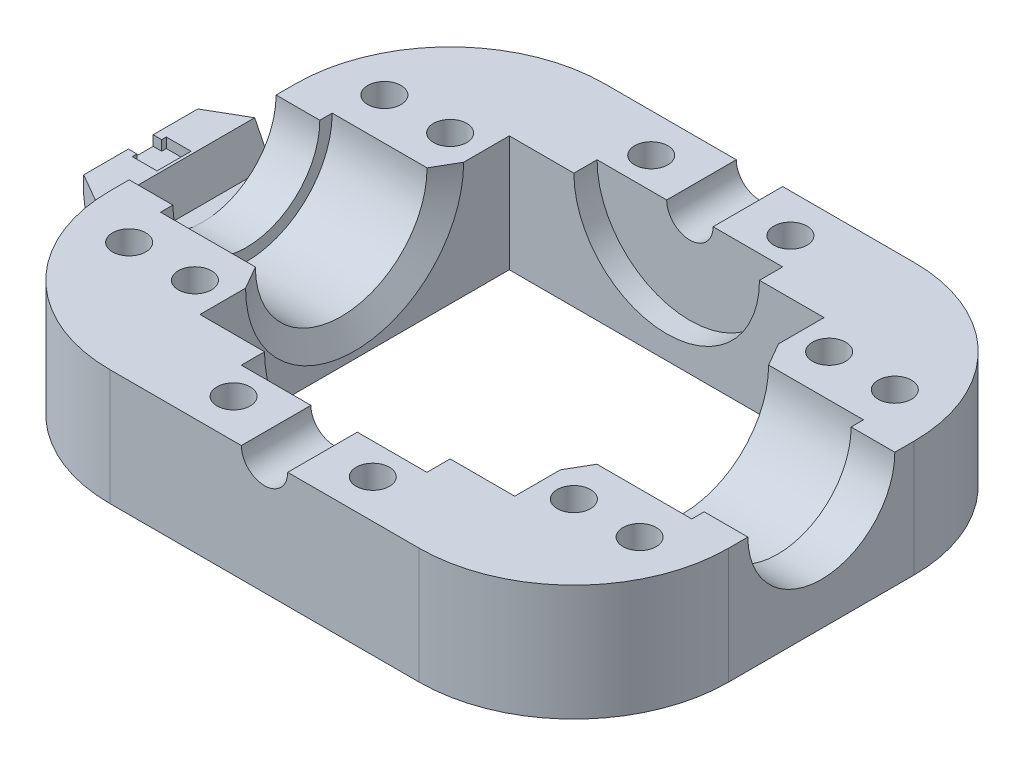
SolidWorks part; units mm, degrees
ref_plane "Спереди" through (0, 0, 0) normal (0, 0, 1) x (1, 0, 0)
ref_plane "Сверху" through (0, 0, 0) normal (0, 1, 0) x (1, 0, 0)
ref_plane "Справа" through (0, 0, 0) normal (1, 0, 0) x (0, 0, -1)
sketch "Sketch1" plane through (0, 0, 0) normal (0, 1, 0) x (1, 0, 0)
  line L1 (40, -32) -> (-40, -32)
  line L2 (40, -32) -> (40, 32)
  line L3 (40, 32) -> (-40, 32)
  line L4 (-40, -32) -> (-40, 32)
  line L5 (40, -32) -> (-40, 32) construction
  line L6 (40, 32) -> (-40, -32) construction
  line L7 (20.35, -20) -> (-20.35, -20)
  line L8 (20.35, -20) -> (20.35, 20)
  line L9 (20.35, 20) -> (-20.35, 20)
  line L10 (-20.35, -20) -> (-20.35, 20)
  line L11 (20.35, -20) -> (-20.35, 20) construction
  line L12 (20.35, 20) -> (-20.35, -20) construction
  point P0 (0, 0)
  point P6 (0, 0)
  dimension "D1" = 80
  dimension "D2" = 64
  dimension "D3" = 40
  dimension "D4" = 40.7
extrude "Boss-Extrude1" add sketch "Sketch1" along normal blind 15
sketch "Sketch3" plane through (0, 15, 0) normal (0, 1, 0) x (1, 0, 0)
  line L0 (-20.35, 0) -> (-40, 0) construction
  line L1 (-20.35, 20) -> (-20.35, -20) construction
  line L2 (-40, 32) -> (-40, -32) construction
  line L3 (20.35, 0) -> (40, 0) construction
  line L4 (20.35, -20) -> (20.35, 20) construction
  line L5 (40, -32) -> (40, 32) construction
  line L10 (20.35, -11.1) -> (34.35, -11.1)
  line L11 (20.35, -11.1) -> (20.35, 0)
  line L12 (20.35, 0) -> (34.35, 0)
  line L13 (34.35, -11.1) -> (34.35, 0)
  line L14 (20.35, -11.1) -> (34.35, 0) construction
  line L15 (20.35, 0) -> (34.35, -11.1) construction
  line L16 (-34.35, -11.1) -> (-20.35, -11.1)
  line L17 (-34.35, -11.1) -> (-34.35, 0)
  line L18 (-34.35, 0) -> (-20.35, 0)
  line L19 (-20.35, -11.1) -> (-20.35, 0)
  line L20 (-34.35, -11.1) -> (-20.35, 0) construction
  line L21 (-34.35, 0) -> (-20.35, -11.1) construction
  point P18 (27.35, -5.55)
  point P23 (-27.35, -5.55)
  dimension "D1" = 14
  dimension "D2" = 11.1
revolve "Cut-Revolve1" cut sketch "Sketch3" angle 360 about L12
sketch "Sketch4" plane through (40, 0, 0) normal (1, 0, 0) x (0, 0, -1)
  line L0 (-32, 15) -> (32, 15) construction
  circle A0 centre (0, 15) radius 9.5
  dimension "D1" = 19
extrude "Cut-Extrude2" cut sketch "Sketch4" against normal through all
sketch "Sketch5" plane through (0, 0, 32) normal (0, 0, 1) x (1, 0, 0)
  line L0 (-40, 15) -> (40, 15) construction
  circle A0 centre (0, 15) radius 3
  dimension "D1" = 6
extrude "Cut-Extrude3" cut sketch "Sketch5" against normal through all
sketch "Sketch8" plane through (0, 15, 0) normal (0, 1, 0) x (1, 0, 0)
  line L1 (-24.5, -16.5) -> (24.5, -16.5) construction
  line L2 (-24.5, -16.5) -> (-24.5, 16.5) construction
  line L3 (-24.5, 16.5) -> (24.5, 16.5) construction
  line L4 (24.5, -16.5) -> (24.5, 16.5) construction
  line L5 (-24.5, -16.5) -> (24.5, 16.5) construction
  line L6 (-24.5, 16.5) -> (24.5, -16.5) construction
  line L7 (-9, 27) -> (9, 27) construction
  line L8 (-9, 27) -> (-9, -27) construction
  line L9 (-9, -27) -> (9, -27) construction
  line L10 (9, 27) -> (9, -27) construction
  line L11 (-9, 27) -> (9, -27) construction
  line L12 (-9, -27) -> (9, 27) construction
  line L13 (33, -16.5) -> (-33, -16.5) construction
  line L14 (33, -16.5) -> (33, 16.5) construction
  line L15 (33, 16.5) -> (-33, 16.5) construction
  line L16 (-33, -16.5) -> (-33, 16.5) construction
  line L17 (33, -16.5) -> (-33, 16.5) construction
  line L18 (33, 16.5) -> (-33, -16.5) construction
  circle A0 centre (24.5, 16.5) radius 2.15
  circle A1 centre (24.5, -16.5) radius 2.15
  circle A2 centre (-24.5, -16.5) radius 2.15
  circle A3 centre (-24.5, 16.5) radius 2.15
  circle A4 centre (9, -27) radius 2.15
  circle A5 centre (-9, -27) radius 2.15
  circle A6 centre (-9, 27) radius 2.15
  circle A7 centre (9, 27) radius 2.15
  circle A8 centre (-33, 16.5) radius 2.15
  circle A9 centre (-33, -16.5) radius 2.15
  circle A10 centre (33, -16.5) radius 2.15
  circle A11 centre (33, 16.5) radius 2.15
  point P0 (0, 0)
  point P10 (0, 0)
  point P16 (0, 0)
  dimension "D3" = 4.3
  dimension "D1" = 33
  dimension "D2" = 49
  dimension "D4" = 18
  dimension "D5" = 54
  dimension "D6" = 66
extrude "Cut-Extrude6" cut sketch "Sketch8" against normal through all
fillet "Fillet1" radius 20 4 edges at (-40, 7.5, 32) (-40, 7.5, -32) (40, 7.5, -32) (40, 7.5, 32)
chamfer "Chamfer1" distance 3 angle 30 2 edges at (-20.35, 3.9, 0) (20.35, 3.9, 0) first distance on face at (-20.35, 8.15, 0) first distance on face at (20.35, 8.15, 0)
sketch "Sketch9" plane through (0, 15, 0) normal (0, 1, 0) x (1, 0, 0)
  line L0 (0, 29.8714) -> (0, -31.0419) construction
  line L1 (-3, 20) -> (-20.35, 20) construction
  line L2 (-12, -23) -> (0, -23)
  line L3 (-12, -23) -> (-12, -20)
  line L4 (-12, -20) -> (0, -20)
  line L5 (0, -23) -> (0, -20)
  line L6 (-12, -23) -> (0, -20) construction
  line L7 (-12, -20) -> (0, -23) construction
  line L8 (-12, 20) -> (0, 20)
  line L9 (-12, 20) -> (-12, 23)
  line L10 (-12, 23) -> (0, 23)
  line L11 (0, 20) -> (0, 23)
  line L12 (-12, 20) -> (0, 23) construction
  line L13 (-12, 23) -> (0, 20) construction
  line L14 (-20.35, -20) -> (-3, -20) construction
  point P3 (-6, -21.5)
  point P8 (-6, 21.5)
  dimension "D1" = 3
  dimension "D2" = 12
revolve "Cut-Revolve2" cut sketch "Sketch9" angle 360 about L0 other way angle 360
sketch "Sketch10" plane through (-40, 0, 0) normal (-1, 0, 0) x (0, 0, 1)
  line L0 (-9.5, 15) -> (9.5, 15) construction
  line L1 (0, 15) -> (0, 0) construction
  line L2 (-12, 0) -> (12, 0) construction
  line L4 (12, 5.5) -> (-12, 5.5)
  line L5 (12, 5.5) -> (12, 0)
  line L6 (12, 0) -> (-12, 0)
  line L7 (-12, 5.5) -> (-12, 0)
  line L8 (12, 5.5) -> (-12, 0) construction
  line L9 (12, 0) -> (-12, 5.5) construction
  arc A0 (-9.5, 15) -> (9.5, 15) centre (0, 15) ccw construction
  point P8 (0, 2.75)
extrude "Boss-Extrude2" add sketch "Sketch10" along normal blind 8
sketch "Sketch12" plane through (-40, 0, 0) normal (-1, 0, 0) x (0, 0, 1)
  line L0 (-9.5, 15) -> (9.5, 15) construction
  line L1 (0, 15) -> (0, 0) construction
  line L3 (12, 9.2) -> (-12, 9.2)
  line L4 (12, 9.2) -> (12, 5.5)
  line L5 (12, 5.5) -> (-12, 5.5)
  line L6 (-12, 9.2) -> (-12, 5.5)
  line L7 (12, 9.2) -> (-12, 5.5) construction
  line L8 (12, 5.5) -> (-12, 9.2) construction
  point P7 (0, 7.35)
  dimension "D1" = 5.8
extrude "Boss-Extrude3" add sketch "Sketch12" along normal up to surface (8 mm away) from offset 2 up to face at (-48, 2.75, 0)
sketch "Sketch13" plane through (0, 9.2, 0) normal (0, 1, 0) x (1, 0, 0)
  line L0 (-42, 0) -> (-48, 0) construction
  line L1 (-42, -12) -> (-42, 12) construction
  line L2 (-48, 12) -> (-48, -12) construction
  line L3 (-46.9, 2.2) -> (-46.9, 1.6)
  line L4 (-46.9, -2.2) -> (-43.7, -2.2)
  line L5 (-46.9, 1.6) -> (-48, 1.6)
  line L6 (-46.9, 2.2) -> (-43.7, 2.2)
  line L7 (-43.7, -2.2) -> (-43.7, 2.2)
  line L8 (-46.9, -2.2) -> (-43.7, 2.2) construction
  line L9 (-46.9, 2.2) -> (-43.7, -2.2) construction
  line L10 (-46.9, -2.2) -> (-46.9, -1.6)
  line L11 (-46.9, -1.6) -> (-48, -1.6)
  line L12 (-48, -1.6) -> (-48, -12)
  line L13 (-48, -12) -> (-42, -12)
  line L14 (-42, -12) -> (-42, 12)
  line L15 (-42, 12) -> (-48, 12)
  line L16 (-48, 12) -> (-48, 1.6)
  point P6 (-45.3, 0)
  dimension "D1" = 3.2
  dimension "D2" = 4.4
  dimension "D3" = 3.2
  dimension "D4" = 2.7
extrude "Boss-Extrude4" add sketch "Sketch13" along normal blind 1.3
chamfer "Chamfer2" distance 5 angle 15 1 edges at (-42, 10.5, 0) first distance on face at (-42, 8, 0)
chamfer "Chamfer3" distance 8 angle 30 2 edges at (-48, 5.25, 12) (-48, 5.25, -12) first distance on face at (-43.5566, 5.3333, 12) first distance on face at (-43.5566, 5.3333, -12)
chamfer "Chamfer4" distance 3 angle 70 1 edges at (-48, 0, 0) first distance on face at (-33, 0, -14.35)
